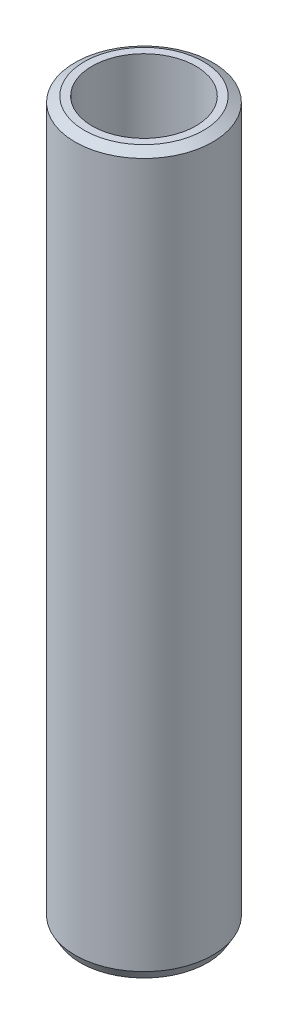
SolidWorks part; units mm, degrees
ref_plane "Front Plane" through (0, 0, 0) normal (0, 0, 1) x (1, 0, 0)
ref_plane "Top Plane" through (0, 0, 0) normal (0, 1, 0) x (1, 0, 0)
ref_plane "Right Plane" through (0, 0, 0) normal (1, 0, 0) x (0, 0, -1)
sketch "Sketch1" plane through (0, 0, 0) normal (0, 1, 0) x (1, 0, 0)
  circle A0 centre (0, 0) radius 57.5
  dimension "SHAFT_OD" = 115
extrude "Boss-Extrude1" add sketch "Sketch1" along normal blind 600
sketch "Sketch2" plane through (0, 0, 0) normal (0, 1, 0) x (1, 0, 0)
  circle A0 centre (0, 0) radius 43.2917
  dimension "BORE_D" = 86.5833
extrude "Cut-Extrude1" cut sketch "Sketch2" along normal through all
chamfer "Chamfer1" distance 4.4948 angle 60 2 edges at (0, 600, 57.5) (0, 0, 57.5) first distance on face at (0, 600, 57.5) first distance on face at (0, 0, 43.2917)
